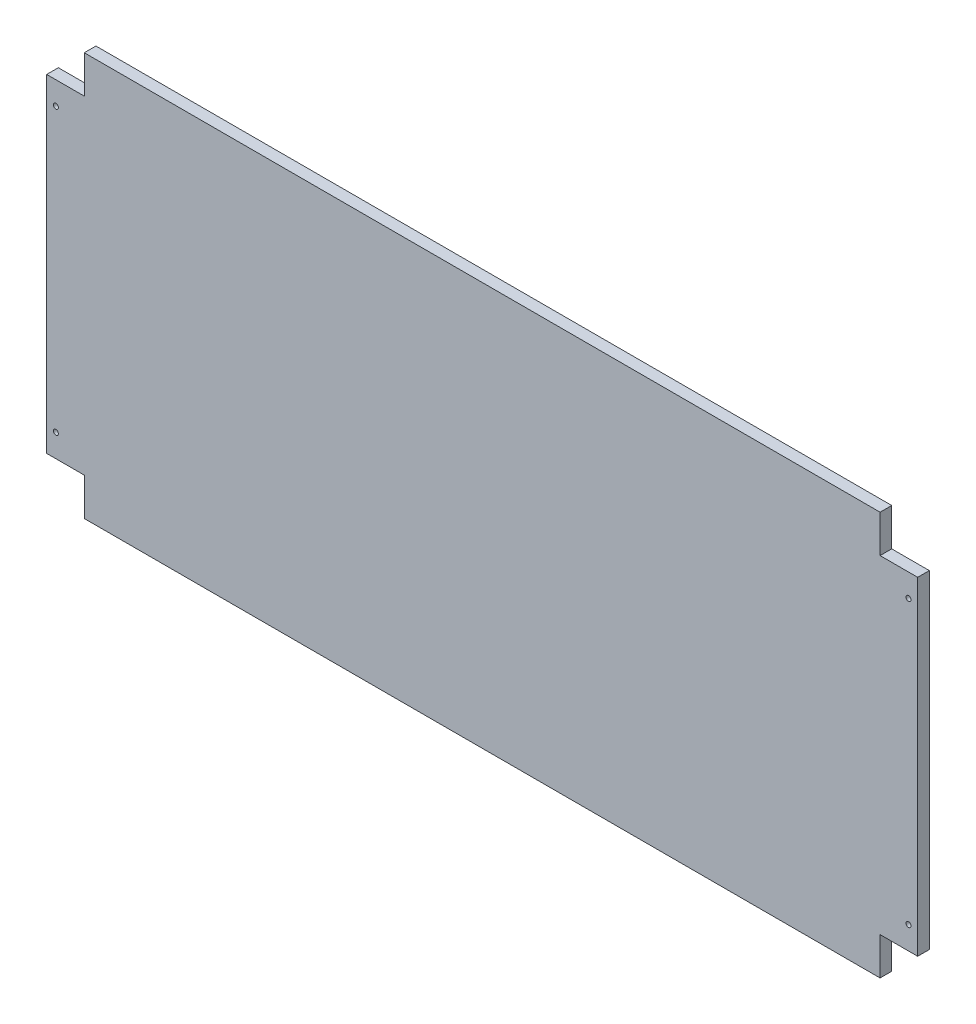
SolidWorks part; units mm, degrees
ref_plane "Front Plane" through (0, 0, 0) normal (0, 0, 1) x (1, 0, 0)
ref_plane "Top Plane" through (0, 0, 0) normal (0, 1, 0) x (1, 0, 0)
ref_plane "Right Plane" through (0, 0, 0) normal (1, 0, 0) x (0, 0, -1)
sketch "Sketch2" plane through (0, 0, 0) normal (0, 0, 1) x (1, 0, 0)
  line L1 (-475, -220) -> (475, -220)
  line L2 (-475, -220) -> (-475, 220)
  line L3 (-475, 220) -> (475, 220)
  line L4 (475, -220) -> (475, 220)
  line L5 (-475, -220) -> (475, 220) construction
  line L6 (-475, 220) -> (475, -220) construction
  point P0 (0, 0)
  dimension "D1" = 950
  dimension "D2" = 440
extrude "Boss-Extrude1" add sketch "Sketch2" along normal blind 12.7
sketch "Sketch3" plane through (0, 0, 12.7) normal (0, 0, 1) x (1, 0, 0)
  line L0 (0, 220) -> (0, -220) construction
  line L1 (-475, 220) -> (-434, 220)
  line L2 (-475, 220) -> (-475, 179)
  line L3 (-475, 179) -> (-434, 179)
  line L4 (-434, 220) -> (-434, 179)
  line L5 (-475, 220) -> (-434, 179) construction
  line L6 (-475, 179) -> (-434, 220) construction
  line L7 (475, 220) -> (-475, 220) construction
  line L8 (-475, -220) -> (475, -220) construction
  line L9 (-475, 0) -> (475, 0) construction
  line L10 (-475, 220) -> (-475, -220) construction
  line L11 (475, -220) -> (475, 220) construction
  line L12 (475, 179) -> (434, 220) construction
  line L13 (475, 220) -> (434, 179) construction
  line L14 (434, 220) -> (434, 179)
  line L15 (475, 179) -> (434, 179)
  line L16 (475, 220) -> (475, 179)
  line L17 (475, 220) -> (434, 220)
  line L18 (475, -220) -> (434, -179) construction
  line L19 (475, -179) -> (434, -220) construction
  line L20 (475, -220) -> (434, -220)
  line L21 (475, -220) -> (475, -179)
  line L22 (434, -220) -> (434, -179)
  line L23 (475, -179) -> (434, -179)
  line L24 (-475, -179) -> (-434, -220) construction
  line L25 (-475, -220) -> (-434, -179) construction
  line L26 (-434, -220) -> (-434, -179)
  line L27 (-475, -179) -> (-434, -179)
  line L28 (-475, -220) -> (-475, -179)
  line L29 (-475, -220) -> (-434, -220)
  point P4 (-454.5, 199.5)
  point P22 (454.5, 199.5)
  point P27 (454.5, -199.5)
  point P32 (-454.5, -199.5)
  dimension "D1" = 41
  dimension "D2" = 41
extrude "Cut-Extrude1" cut sketch "Sketch3" against normal up to next
sketch "Sketch4" plane through (0, 0, 12.7) normal (0, 0, 1) x (1, 0, 0)
  line L0 (-465, 179) -> (-465, -179) construction
  line L1 (-475, 179) -> (-434, 179) construction
  line L2 (-434, -179) -> (-475, -179) construction
  line L3 (0, 220) -> (0, -220) construction
  line L4 (434, 220) -> (-434, 220) construction
  line L5 (-434, -220) -> (434, -220) construction
  line L6 (0, 0) -> (-475, 0) construction
  line L7 (-475, 179) -> (-475, -179) construction
  circle A0 centre (-465, -154) radius 2.75
  circle A1 centre (-465, 154) radius 2.75
  circle A2 centre (465, -154) radius 2.75
  circle A3 centre (465, 154) radius 2.75
  dimension "D1" = 5.5
  dimension "D2" = 25
  dimension "D3" = 10
extrude "Cut-Extrude2" cut sketch "Sketch4" against normal up to next
